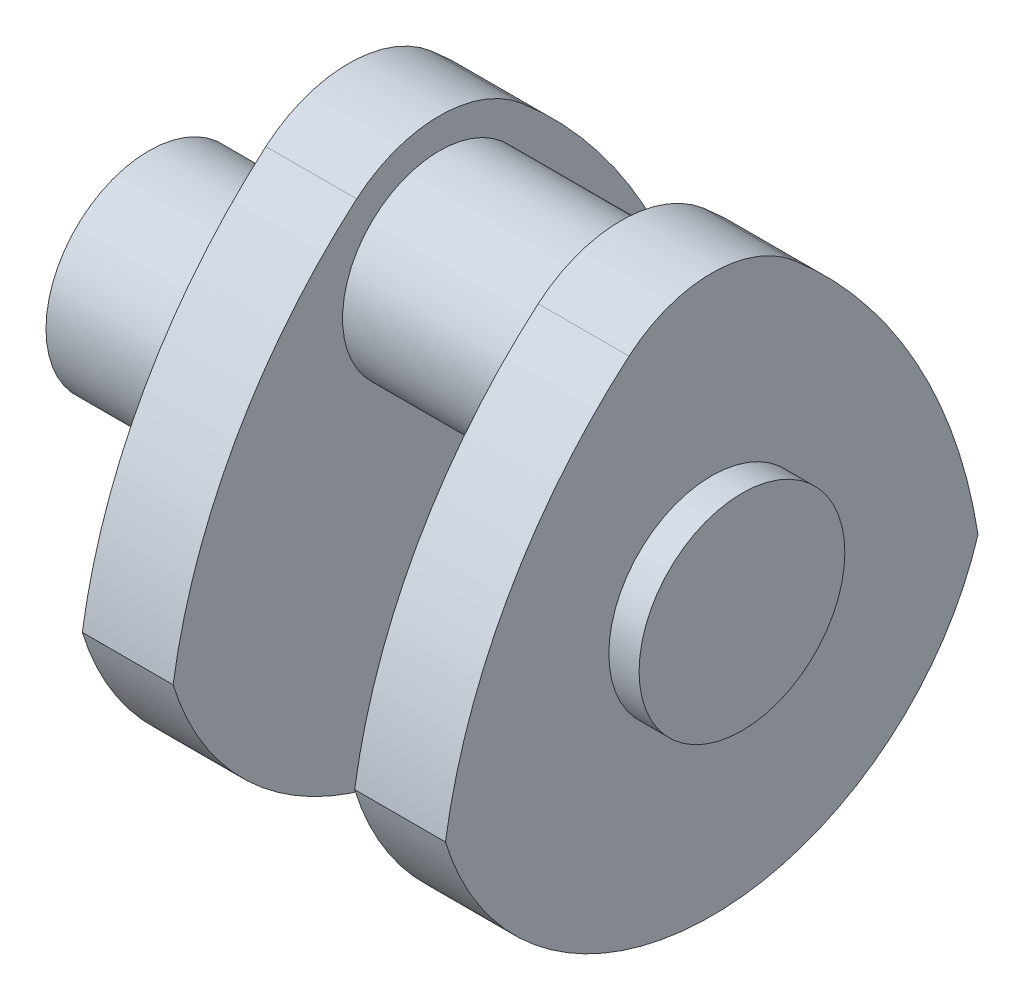
SolidWorks part; units mm, degrees
ref_plane "Front Plane" through (0, 0, 0) normal (0, 0, 1) x (1, 0, 0)
ref_plane "Top Plane" through (0, 0, 0) normal (0, 1, 0) x (1, 0, 0)
ref_plane "Right Plane" through (0, 0, 0) normal (1, 0, 0) x (0, 0, -1)
sketch "Sketch1" plane through (0, 0, 0) normal (1, 0, 0) x (0, 0, -1)
  circle A0 centre (0, 0) radius 19
  circle A1 centre (0, 0) radius 17
  dimension "D1" = 38
  dimension "D2" = 34
extrude "Boss-Extrude1" add sketch "Sketch1" against normal blind 25 contours A1 region at (0, 0, 0)
extrude "Boss-Extrude5" add sketch "Sketch1<6>" along normal blind 8 contours A1 | A0 A1 region at (0, 0, 18.4626) region at (0, 0, 0)
sketch "Sketch1<6>" plane through (0, 0, 0) normal (1, 0, 0) x (0, 0, -1) same geometry as "Sketch1"
sketch "Sketch2" plane through (8, 0, 0) normal (1, 0, 0) x (0, 0, -1)
  arc A0 (-13.6681, 40.9431) -> (13.6681, 40.9431) centre (0, 25) cw
  arc A4 (44, -13.4164) -> (-44, -13.4164) centre (0, 0) cw
  arc A5 (-13.6681, 40.9431) -> (-44, -13.4164) centre (44.9095, -27.3845) ccw
  arc A6 (13.6681, 40.9431) -> (44, -13.4164) centre (-44.9095, -27.3845) cw
  point P8 (0, 0)
  point P9 (0, 0)
  point P11 (0, 0)
  point P12 (0, 0)
  point P13 (0, 0)
  point P14 (0, 0)
  point P15 (0, 0)
  dimension "D2" = 21
  dimension "D3" = 90
  dimension "D4" = 90
  dimension "D6" = 46
  dimension "D1" = 88
  dimension "D5" = 25
extrude "Boss-Extrude6" add sketch "Sketch2" along normal blind 15
sketch "Sketch4" plane through (23, 0, 0) normal (1, 0, 0) x (0, 0, -1)
  circle A0 centre (0, 25) radius 16
  dimension "D1" = 32
extrude "Boss-Extrude7" add sketch "Sketch4" along normal blind 15
mirror "Mirror1" about plane through (38, 25, 0) normal (1, 0, 0) of "Boss-Extrude7", "Boss-Extrude6"
sketch "Sketch5" plane through (68, 0, 0) normal (1, 0, 0) x (0, 0, -1)
  circle A0 centre (0, 0) radius 17
  dimension "D1" = 34
extrude "Boss-Extrude8" add sketch "Sketch5" along normal blind 5
